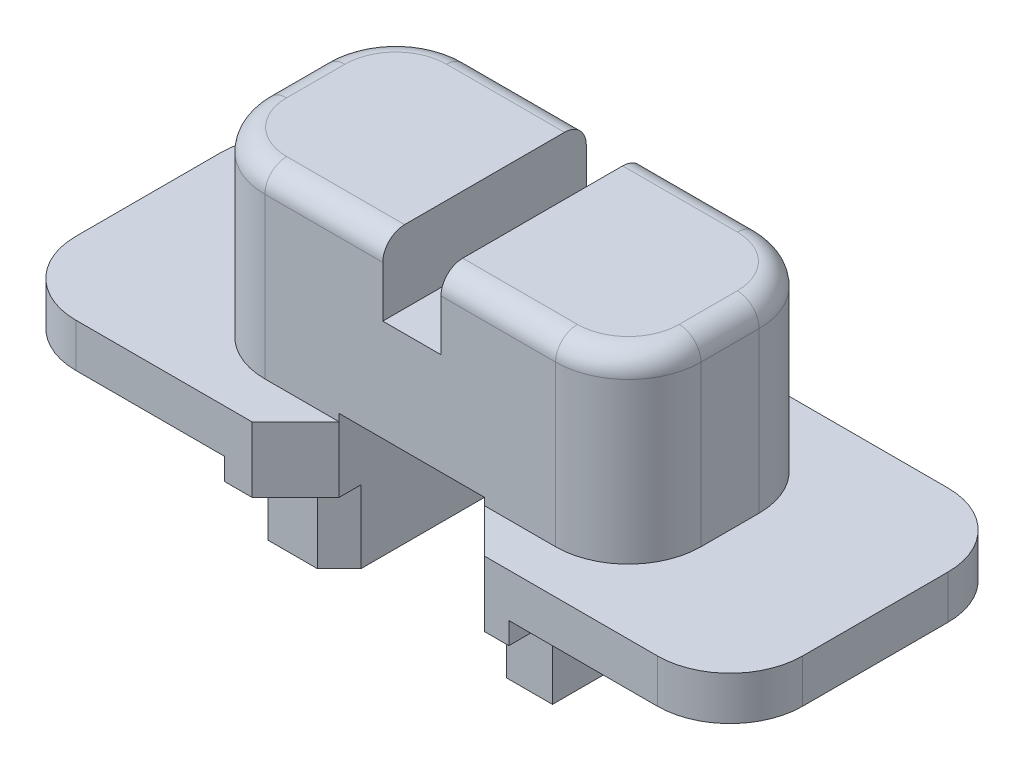
SolidWorks part; units mm, degrees
ref_plane "前视基准面" through (0, 0, 0) normal (0, 0, 1) x (1, 0, 0)
ref_plane "上视基准面" through (0, 0, 0) normal (0, 1, 0) x (1, 0, 0)
ref_plane "右视基准面" through (0, 0, 0) normal (1, 0, 0) x (0, 0, -1)
sketch "草图1" plane through (0, 0, 0) normal (0, 1, 0) x (1, 0, 0)
  line L1 (-4.5475, 2) -> (5.4525, 2)
  line L2 (-4.5475, 2) -> (-4.5475, -2)
  line L3 (-4.5475, -2) -> (5.4525, -2)
  line L4 (5.4525, 2) -> (5.4525, -2)
  line L5 (-4.5475, 2) -> (5.4525, -2) construction
  line L6 (-4.5475, -2) -> (5.4525, 2) construction
  point P0 (0.4525, 0)
  dimension "D1" = 10
  dimension "D2" = 4
extrude "凸台-拉伸1" add sketch "草图1" along normal blind 0.6
sketch "草图2" plane through (0, 0.6, 0) normal (0, 1, 0) x (1, 0, 0)
  line L1 (-2.5475, 1.4) -> (3.4525, 1.4)
  line L2 (-2.5475, 1.4) -> (-2.5475, -1.4)
  line L3 (-2.5475, -1.4) -> (3.4525, -1.4)
  line L4 (3.4525, 1.4) -> (3.4525, -1.4)
  line L5 (-2.5475, 1.4) -> (3.4525, -1.4) construction
  line L6 (-2.5475, -1.4) -> (3.4525, 1.4) construction
  line L7 (5.4525, -2) -> (5.4525, 2) construction
  point P0 (0.4525, 0)
  point P12 (5.4525, 0)
  dimension "D1" = 2.8
  dimension "D2" = 6
extrude "凸台-拉伸2" add sketch "草图2" along normal blind 2.5
fillet "圆角1" radius 1 8 edges at (-4.5475, 0.3, 2) (-2.5475, 1.85, 1.4) (5.4525, 0.3, 2) (3.4525, 1.85, 1.4) (-2.5475, 1.85, -1.4) (3.4525, 1.85, -1.4) (5.4525, 0.3, -2) (-4.5475, 0.3, -2)
sketch "草图7" plane through (0, 0, 1.4) normal (0, 0, 1) x (1, 0, 0)
  line L0 (-1.5475, 3.1) -> (2.4525, 3.1) construction
  line L1 (0.8748, 2.1) -> (0.0748, 2.1)
  line L2 (0.8748, 2.1) -> (0.8748, 3.1)
  line L3 (0.8748, 3.1) -> (0.0748, 3.1)
  line L4 (0.0748, 2.1) -> (0.0748, 3.1)
  line L5 (0.8748, 2.1) -> (0.0748, 3.1) construction
  line L6 (0.8748, 3.1) -> (0.0748, 2.1) construction
  point P0 (0.4748, 2.6)
  dimension "D1" = 0.8
extrude "切除-拉伸2" cut sketch "草图7" against normal up to next and the other way through all
sketch "草图8" plane through (0, 0, 0) normal (0, -1, 0) x (1, 0, 0)
  line L0 (-3.5475, 2) -> (4.4525, 2) construction
  line L1 (-1.5043, 2) -> (2.4092, 2)
  line L2 (-1.5043, 2) -> (-1.5043, -2)
  line L3 (-1.5043, -2) -> (2.4092, -2)
  line L4 (2.4092, 2) -> (2.4092, -2)
  line L5 (-1.5043, 2) -> (2.4092, -2) construction
  line L6 (-1.5043, -2) -> (2.4092, 2) construction
  line L7 (4.4525, -2) -> (-3.5475, -2) construction
  point P0 (0.4525, 0)
  point P7 (0.4525, 2)
extrude "凸台-拉伸3" add sketch "草图8" along normal blind 0.3
sketch "草图9" plane through (0, 0, -2) normal (0, 0, -1) x (-1, 0, 0)
  line L0 (1.5043, -0.3) -> (-2.4092, -0.3) construction
  line L1 (-1.4748, -0.3) -> (0.5252, -0.3)
  line L2 (-1.4748, -0.3) -> (-1.4748, 0.7)
  line L3 (-1.4748, 0.7) -> (0.5252, 0.7)
  line L4 (0.5252, -0.3) -> (0.5252, 0.7)
  line L5 (-0.0748, 2.1) -> (-0.8748, 2.1) construction
  point P6 (-0.4748, 0.7)
  point P9 (-0.4748, 2.1)
  dimension "D1" = 2
  dimension "D2" = 1
extrude "切除-拉伸3" cut sketch "草图9" against normal up to next
chamfer "倒角2" distance 0.6 angle 45 4 edges at (-0.5252, 0.15, 2) (-0.5252, 0.15, -2) (1.4748, 0.15, -2) (1.4748, 0.15, 2)
fillet "圆角2" radius 0.3 10 edges at (1.6636, 3.1, 1.4) (3.1596, 3.1, 1.1071) (3.4525, 3.1, 0) (1.6636, 3.1, -1.4) (-0.7364, 3.1, -1.4) (-0.7364, 3.1, 1.4) (-2.2546, 3.1, 1.1071) (-2.5475, 3.1, 0) (3.1596, 3.1, -1.1071) (-2.2546, 3.1, -1.1071)
sketch "草图10" plane through (0, -0.3, 0) normal (0, -1, 0) x (1, 0, 0)
  line L0 (-1.1252, -2) -> (-0.5252, -1.4) construction
  line L1 (-0.5252, -1.4) -> (-1.5043, -1.4)
  line L2 (-0.5252, -1.4) -> (-0.5252, 1.4)
  line L3 (-0.5252, 1.4) -> (-1.5043, 1.4)
  line L4 (-1.5043, -1.4) -> (-1.5043, 1.4)
  line L5 (-0.5252, 1.4) -> (-0.5252, -1.4) construction
  line L6 (-1.5043, 2) -> (-1.5043, -2) construction
  line L7 (1.4748, 1.4) -> (1.4748, -1.4) construction
  line L8 (1.4748, -1.4) -> (2.4092, -1.4)
  line L9 (1.4748, -1.4) -> (1.4748, 1.4)
  line L10 (1.4748, 1.4) -> (2.4092, 1.4)
  line L11 (2.4092, -1.4) -> (2.4092, 1.4)
  line L12 (2.4092, -2) -> (2.4092, 2) construction
extrude "凸台-拉伸4" add sketch "草图10" along normal blind 1
chamfer "倒角3" distance 0.3 angle 45 4 edges at (1.4748, -0.8, -1.4) (-0.5252, -0.8, -1.4) (1.4748, -0.8, 1.4) (-0.5252, -0.8, 1.4)
